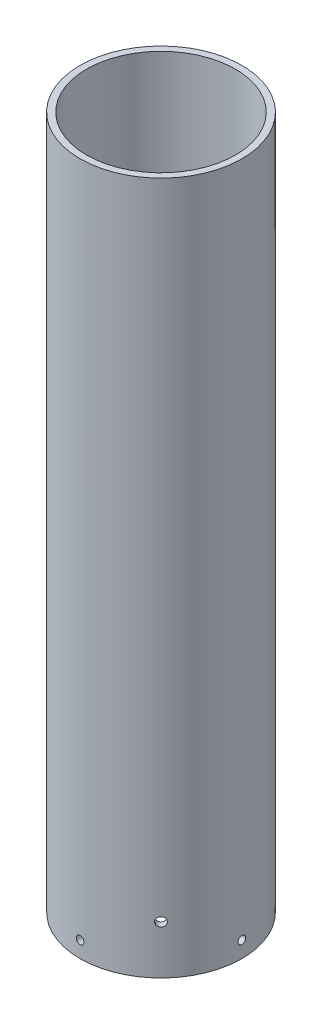
SolidWorks part; units mm, degrees
material "ПВХ 0.007 Смягченный"
ref_plane "Спереди" through (0, 0, 0) normal (0, 0, 1) x (1, 0, 0)
ref_plane "Сверху" through (0, 0, 0) normal (0, 1, 0) x (1, 0, 0)
ref_plane "Справа" through (0, 0, 0) normal (1, 0, 0) x (0, 0, -1)
sketch "Эскиз1" plane through (0, 0, 0) normal (0, 1, 0) x (1, 0, 0)
  circle A0 centre (0, 0) radius 25
  circle A1 centre (0, 0) radius 23
  dimension "ExDBody" = 50
  dimension "InDBody" = 46
extrude "Бобышка-Вытянуть1" add sketch "Эскиз1" along normal blind 214
sketch "Эскиз5" plane through (0, 0, 0) normal (0, 0, 1) x (1, 0, 0)
  circle A0 centre (0, 5) radius 1.2
  dimension "D1" = 2.4
  dimension "D2" = 5
extrude "Вырез-Вытянуть5" cut sketch "Эскиз5" against normal through all
pattern_circular "Круговой массив1" count 4 over 360 about axis through (0, 214, 0) along (0, -1, 0) of "Вырез-Вытянуть5" reverse direction yes
ref_plane "Плоскость1" through (0, 0, 0) normal (-0.7071, 0, 0.7071) x (0, -1, 0)
sketch "Эскиз6" plane through (0, 0, 0) normal (-0.7071, 0, 0.7071) x (0, -1, 0)
  line L0 (-214, 0) -> (0, 0) construction
  line L1 (0, -25) -> (0, 25) construction
  circle A0 centre (-15, 0) radius 1.4
  dimension "D1" = 15
extrude "Вырез-Вытянуть6" cut sketch "Эскиз6" against normal through all
pattern_circular "Круговой массив2" count 4 over 360 about axis through (0, 214, 0) along (0, -1, 0) of "Вырез-Вытянуть6"
